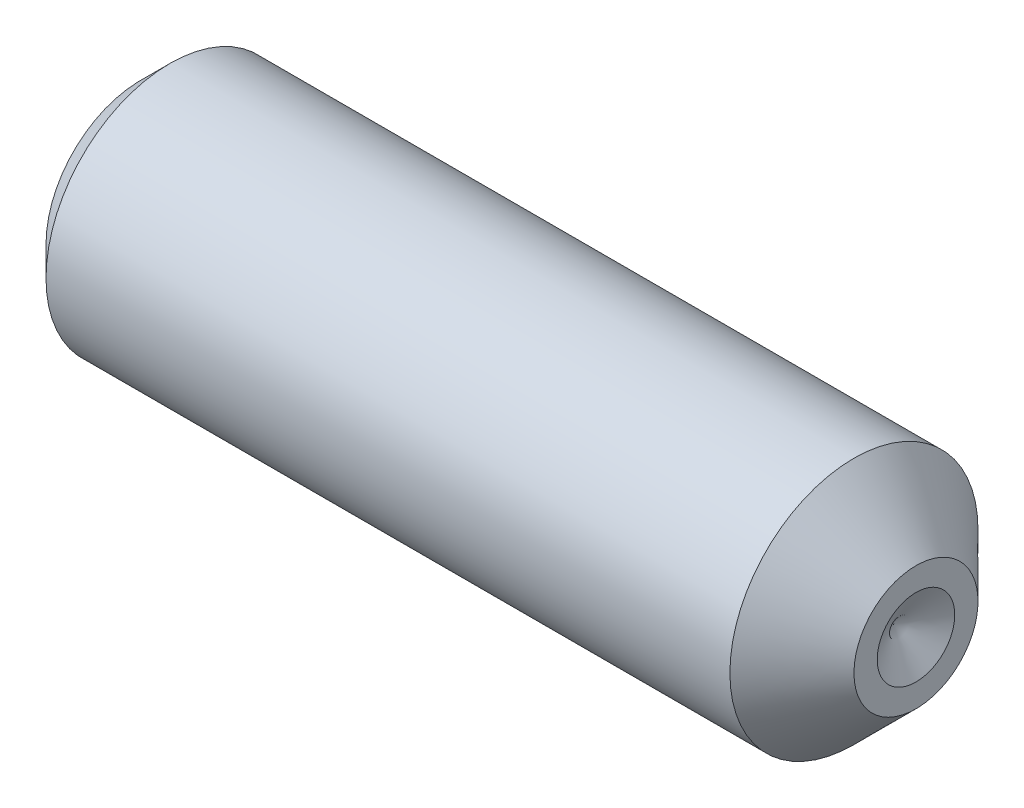
SolidWorks part; units mm, degrees
ref_plane "Front" through (0, 0, 0) normal (0, 0, 1) x (1, 0, 0)
ref_plane "Top" through (0, 0, 0) normal (0, 1, 0) x (1, 0, 0)
ref_plane "Right" through (0, 0, 0) normal (1, 0, 0) x (0, 0, -1)
sketch "Sketch1" plane through (0, 0, 0) normal (0, 0, 1) x (1, 0, 0)
  line L0 (0, 0) -> (5, 0)
  line L1 (5, 0) -> (5, 0.4)
  line L2 (5, 0.4) -> (4.6, 0.8)
  line L3 (4.6, 0.8) -> (0.1895, 0.8)
  line L4 (0.1895, 0.8) -> (0, 0.6105)
  line L5 (0, 0.6105) -> (0, 0)
  line L6 (-10.745, 0) -> (0.8952, 0) construction
  dimension "D2" = 45
  dimension "D1" = 45
revolve "Base" add sketch "Sketch1" angle 360 about L6
cosmetic thread "ThreadCosmetic1" [suppressed] parameters "D2"=1.4
sketch "Sketch2" plane through (0, 0.1805, -0.2958) normal (-1, 0, 0) x (0, 0, 1)
  line L1 (0.6999, -0.1805) -> (0.4979, 0.1695)
  line L2 (0.4979, 0.1695) -> (0.0937, 0.1695)
  line L3 (0.0937, 0.1695) -> (-0.1084, -0.1805)
  line L4 (-0.1084, -0.1805) -> (0.0937, -0.5305)
  line L5 (0.0937, -0.5305) -> (0.4979, -0.5305)
  line L6 (0.4979, -0.5305) -> (0.6999, -0.1805)
  circle A0 centre (0.2958, -0.1805) radius 0.35 construction
  dimension "s" = 0.7
extrude "HexagonSocket" cut sketch "Sketch2" against normal blind 0.7
sketch "Sketch3" plane through (5, -0.0018, -0.0116) normal (1, 0, 0) x (0, 0, -1)
  circle A0 centre (-0.0116, 0.0018) radius 0.25
  circle A1 centre (-0.0116, 0.0018) radius 0.4 construction
  dimension "D1" = 0.5
extrude "Cut-Extrude1" cut sketch "Sketch3" against normal blind 10 draft 60
sketch "Sketch4" plane through (0, 0, 0) normal (0, 0, 1) x (1, 0, 0)
  line L0 (0.2372, 0) -> (-5.2372, 0) construction
  line L2 (0.7, 0.35) -> (0.9021, 0)
  line L3 (0.9021, 0) -> (0.7, 0)
  line L4 (0.7, 0) -> (0.7, 0.35)
  dimension "D1" = 60
revolve "Cut-Revolve1" cut sketch "Sketch4" angle 360 about L0
sketch "Sketch5" plane through (0, 0, 0) normal (0, 0, 1) x (1, 0, 0)
  line L0 (0.1895, 0.7134) -> (0.2395, 0.8)
  line L1 (0.2395, 0.8) -> (0.2395, 0.9)
  line L2 (0.2395, 0.9) -> (0.1395, 0.9)
  line L3 (0.1395, 0.9) -> (0.1395, 0.8)
  line L4 (0.1395, 0.8) -> (0.1895, 0.7134)
  line L5 (0.1895, 0.8) -> (0.1895, -0.8) construction
  line L6 (0, 0) -> (2.2912, 0) construction
  line L7 (0, 0.6105) -> (0, -0.6105) construction
  dimension "D1" = 1.6
  dimension "D2" = 0.1
revolve "Cut-Revolve10" [suppressed] cut sketch "Sketch5" angle 360 about L6
pattern_linear "LPattern10" [suppressed] count 40 spacing 0.12 along (1, 0, 0) of bodies 105
equation "\"D1@Sketch3\" = \"dz@Sketch1\" - 0.3"
equation "\"D1@Sketch5\" = \"d@Sketch1\""
equation "\"D2@Sketch5\" =  ( \"d@Sketch1\" - \"D2@ThreadCosmetic1\" )  / 2"
equation "\"D3@LPattern10\" = \"D2@Sketch5\" * 1.2"
equation "\"D1@LPattern10\" = (  \"l@Sketch1\" -  ( \"d@Sketch1\" - \"df@Sketch1\" )  / 2 )  / \"D3@LPattern10\""
